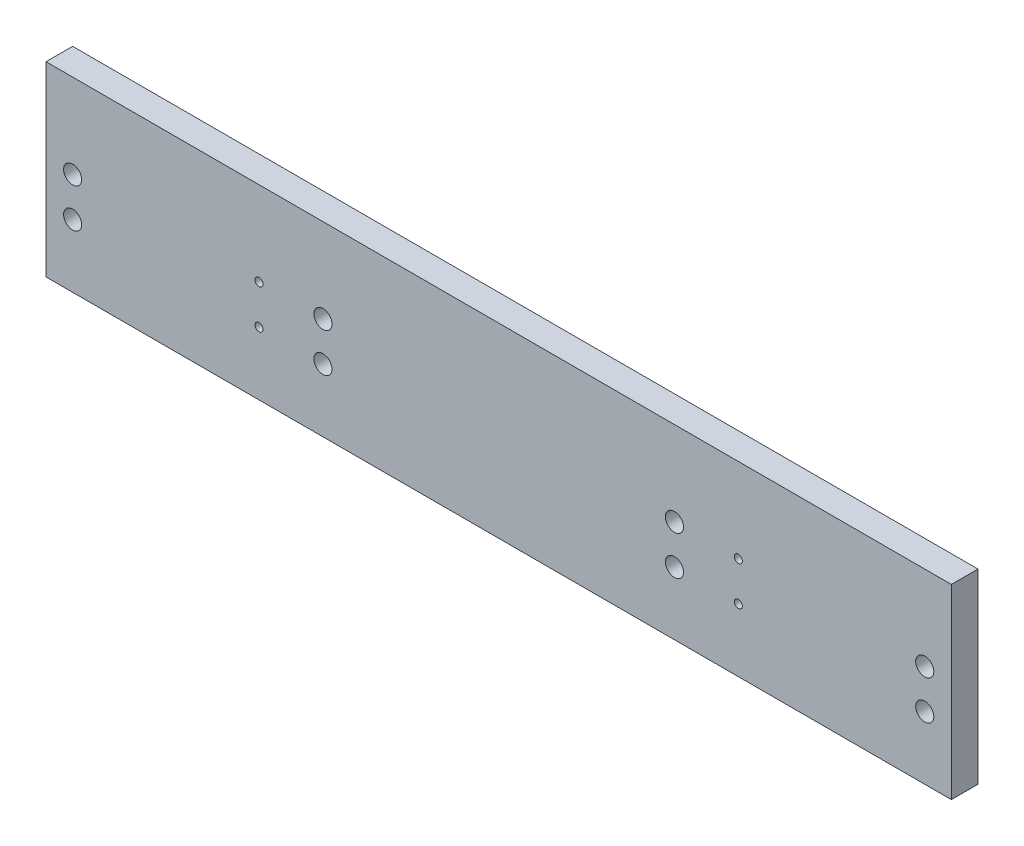
SolidWorks part; units mm, degrees
material "Plain Carbon Steel"
ref_plane "Front Plane" through (0, 0, 0) normal (0, 0, 1) x (1, 0, 0)
ref_plane "Top Plane" through (0, 0, 0) normal (0, 1, 0) x (1, 0, 0)
ref_plane "Right Plane" through (0, 0, 0) normal (1, 0, 0) x (0, 0, -1)
sketch "Sketch1" plane through (0, 0, 0) normal (0, 0, 1) x (1, 0, 0)
  line L0 (100, -37.7497) -> (100, 151.1829) construction
  line L1 (-70, 63) -> (270, 63)
  line L2 (-70, 63) -> (-70, -7)
  line L3 (-70, -7) -> (270, -7)
  line L4 (270, 63) -> (270, -7)
  line L5 (270, 28) -> (-70, 28) construction
  line L6 (100, 63) -> (100, -7) construction
  line L7 (-50, 2) -> (-50, 46) construction
  line L8 (-47, 63) -> (-10, 63) construction
  line L9 (247, -7) -> (-47, -7) construction
  point P4 (100, 63)
  point P17 (100, 28)
  dimension "D3" = 20
extrude "Boss-Extrude1" add sketch "Sketch1" along normal blind 10
hole_wizard "M8 Tapped Hole1" positions "Sketch2" profile "Sketch3" tap size "M8" standard "ISO"
sketch "Sketch2" plane through (99.6589, 53.9855, 20) normal (0, 0, 1) x (1, 0, 0)
  point P0 (-159.6589, -22.6522)
  point P3 (-159.6589, -37.3188)
  point P6 (-65.6589, -22.6522)
  point P9 (-65.6589, -37.3188)
  point P12 (66.3411, -22.6522)
  point P15 (66.3411, -37.3188)
  point P18 (160.3411, -22.6522)
  point P21 (160.3411, -37.3188)
sketch "Sketch3" plane through (-60, 31.3333, 20) normal (1, 0, 0) x (0, -1, 0)
  line L0 (0, 0) -> (0, 72.0419)
  line L1 (0, 72.0419) -> (3.4, 69.999)
  line L2 (3.4, 69.999) -> (3.4, 0)
  line L3 (3.4, 0) -> (0, 0)
  line L4 (0, 72.0419) -> (-3.4, 69.999) construction
  line L5 (0, -6.35) -> (0, 107.95) construction
  dimension "Tap Drill Dia." = 6.8
  dimension "Tap Drill Depth" = 69.999
  dimension "Drill Angle" = 118
hole_wizard "M8 Tapped Hole2" positions "Sketch4" profile "Sketch5" tap size "M8" standard "ISO"
sketch "Sketch4" plane through (100.3411, 53.9855, 0) normal (0, 0, -1) x (-1, 0, 0)
  point P0 (-159.6589, -22.6522)
  point P3 (-159.6589, -37.3188)
  point P6 (-65.6589, -22.6522)
  point P9 (-65.6589, -37.3188)
  point P12 (66.3411, -22.6522)
  point P15 (66.3411, -37.3188)
  point P18 (160.3411, -22.6522)
  point P21 (160.3411, -37.3188)
sketch "Sketch5" plane through (260, 31.3333, 0) normal (1, 0, 0) x (0, 1, 0)
  line L0 (0, 0) -> (0, 72.0419)
  line L1 (0, 72.0419) -> (3.4, 69.999)
  line L2 (3.4, 69.999) -> (3.4, 0)
  line L3 (3.4, 0) -> (0, 0)
  line L4 (0, 72.0419) -> (-3.4, 69.999) construction
  line L5 (0, -6.35) -> (0, 107.95) construction
  dimension "Tap Drill Dia." = 6.8
  dimension "Tap Drill Depth" = 69.999
  dimension "Drill Angle" = 118
hole_wizard "Ø3.0 (3) Diameter Hole1" positions "Sketch6" profile "Sketch7" hole size "Ø3.0" standard "ISO"
sketch "Sketch6" plane through (99.6589, 53.9855, 20) normal (0, 0, 1) x (1, 0, 0)
  point P0 (-89.6589, -22.6522)
  point P3 (-89.6589, -37.3188)
  point P6 (90.3411, -22.6522)
  point P9 (90.3411, -37.3188)
sketch "Sketch7" plane through (10, 31.3333, 20) normal (1, 0, 0) x (0, -1, 0)
  line L0 (0, 0) -> (0, 30.9013)
  line L1 (0, 30.9013) -> (1.5, 30)
  line L2 (1.5, 30) -> (1.5, 0)
  line L3 (1.5, 0) -> (0, 0)
  line L4 (0, 30.9013) -> (-1.5, 30) construction
  line L5 (0, -6.35) -> (0, 107.95) construction
  dimension "Hole Dia." = 3
  dimension "Hole Depth" = 30
  dimension "Drill Angle" = 118
hole_wizard "Ø3.0 (3) Diameter Hole2" positions "Sketch8" profile "Sketch9" hole size "Ø3.0" standard "ISO"
sketch "Sketch8" plane through (100.3411, 53.9855, 0) normal (0, 0, -1) x (-1, 0, 0)
  point P0 (-89.6589, -22.6522)
  point P3 (-89.6589, -37.3188)
  point P6 (90.3411, -22.6522)
  point P9 (90.3411, -37.3188)
sketch "Sketch9" plane through (190, 31.3333, 0) normal (1, 0, 0) x (0, 1, 0)
  line L0 (0, 0) -> (0, 30.9013)
  line L1 (0, 30.9013) -> (1.5, 30)
  line L2 (1.5, 30) -> (1.5, 0)
  line L3 (1.5, 0) -> (0, 0)
  line L4 (0, 30.9013) -> (-1.5, 30) construction
  line L5 (0, -6.35) -> (0, 107.95) construction
  dimension "Hole Dia." = 3
  dimension "Hole Depth" = 30
  dimension "Drill Angle" = 118
